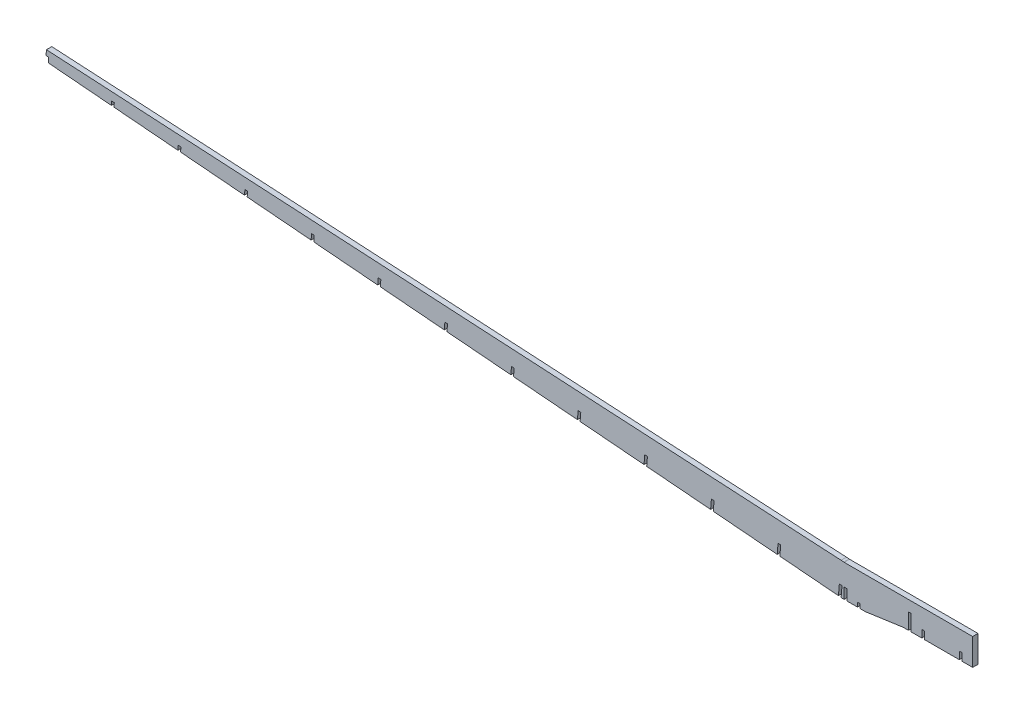
SolidWorks part; units mm, degrees
material "Balsa"
ref_plane "Front Plane" through (0, 0, 0) normal (0, 0, 1) x (1, 0, 0)
ref_plane "Top Plane" through (0, 0, 0) normal (0, 1, 0) x (1, 0, 0)
ref_plane "Right Plane" through (0, 0, 0) normal (1, 0, 0) x (0, 0, -1)
sketch "Sketch1" plane through (0, 0, 0) normal (0, 0, 1) x (1, 0, 0)
  line L0 (76.2, 56.7475) -> (76.2, 37.6975)
  line L1 (79.375, 56.7475) -> (79.375, 37.6975)
  line L2 (0, 44.0475) -> (0, 31.3475)
  line L3 (3.175, 44.0475) -> (3.175, 31.3475)
  line L4 (-5.7133, 44.4467) -> (-6.776, 31.7912)
  line L5 (-2.5494, 44.181) -> (-3.6121, 31.5255)
  line L6 (-1.4923, 31.3475) -> (25.4, 31.3475)
  line L7 (25.4, 31.3475) -> (69.85, 37.6975)
  line L8 (-2.5494, 44.181) -> (-0.424, 69.4919) construction
  line L9 (-0.424, 69.4919) -> (-3.5879, 69.7576)
  line L10 (-3.5879, 69.7576) -> (-5.7133, 44.4467) construction
  line L11 (-5.7133, 44.4467) -> (-2.5494, 44.181)
  line L12 (3.175, 44.0475) -> (3.175, 69.4475) construction
  line L13 (3.175, 69.4475) -> (0, 69.4475)
  line L14 (0, 69.4475) -> (0, 44.0475) construction
  line L15 (0, 44.0475) -> (3.175, 44.0475)
  line L16 (92.075, 37.6975) -> (92.075, 46.5875)
  line L17 (-942.8808, 122.7744) -> (-947.5199, 67.5279)
  line L18 (0, 69.4475) -> (-0.424, 69.4919)
  line L19 (3.175, 69.4475) -> (152.4, 69.4475)
  line L20 (152.4, 69.4475) -> (152.4, 37.6975)
  line L21 (152.4, 37.6975) -> (69.85, 37.6975)
  line L22 (92.075, 46.5875) -> (95.25, 46.5875)
  line L23 (95.25, 46.5875) -> (95.25, 37.6975)
  line L24 (-1.4923, 31.3475) -> (-943.9128, 110.4848)
  line L25 (79.375, 69.4475) -> (79.375, 56.7475)
  line L26 (-942.8808, 122.7744) -> (-3.5879, 69.7576)
  line L27 (136.525, 37.6975) -> (136.525, 46.5875)
  line L28 (76.2, 69.4475) -> (76.2, 56.7475)
  line L29 (79.375, 56.7475) -> (76.2, 56.7475)
  line L30 (-943.5688, 114.5813) -> (-5.7133, 44.4467)
  line L31 (136.525, 46.5875) -> (139.7, 46.5875)
  line L32 (139.7, 46.5875) -> (139.7, 37.6975)
  line L33 (15.875, 31.3475) -> (15.875, 36.4275)
  line L34 (15.875, 36.4275) -> (19.05, 36.4275)
  line L35 (19.05, 36.4275) -> (19.05, 31.3475)
  line L36 (-942.8808, 122.7744) -> (-946.0519, 122.9534)
  line L37 (-946.0519, 122.9534) -> (-946.5835, 116.6233)
  line L38 (-946.5835, 116.6233) -> (-943.4123, 116.4443)
  dimension "D3" = 76.2
  dimension "D10" = 12.3329
  dimension "D11" = 8.2219
  dimension "D2" = 25.4
  dimension "D4" = 25.4
  dimension "D5" = 12.7
  dimension "D7" = 3.175
  dimension "D9" = 3.175
  dimension "D12" = 3.175
  dimension "D6" = 19.05
  dimension "D13" = 6.35
  dimension "D14" = 12.7
  dimension "D16" = 3.175
  dimension "D17" = 3.175
  dimension "D18" = 12.7
  dimension "D19" = 12.7
  dimension "D20" = 8.89
  dimension "D21" = 8.89
  dimension "D15" = 76.2
  dimension "D22" = 12.7
  dimension "D23" = 3.175
  dimension "D24" = 5.08
  dimension "D8" = 6.35
  dimension "D25" = 3.175
  dimension "D26" = 6.35
extrude "Boss-Extrude1" add sketch "Sketch1" along normal mid plane 6.35 contours L17 L30 L11 L5 L24 L6 L2 L15 L3 L7 L21 L0 L28 L19 L13 L18 L9 L26 | L30 L17 L24 L4 | L29 L25 L19 L28 | L19 L25 L1 L21 L20 | L37 L38 L17 L36 region at (-328.9931, 77.9728, 0) region at (77.7875, 63.0975, 0) region at (115.8875, 53.8578, 0) region at (-944.7321, 119.6988, 0) region at (-395.1618, 68.9894, 0)
sketch "Sketch2" plane through (0, 0, 3.175) normal (0, 0, 1) x (1, 0, 0)
  line L2 (-73.2652, 73.2231) -> (-80.3969, -11.7061)
  line L3 (-943.5688, 114.5813) -> (-5.7133, 44.4467)
  line L6 (-76.4291, 73.4888) -> (-83.5608, -11.4404)
  line L7 (-6.776, 31.7912) -> (-943.9128, 110.4848)
  line L10 (-152.4177, 77.6821) -> (-159.3225, -4.5442)
  line L14 (-155.5816, 77.9478) -> (-162.4863, -4.2785)
  line L18 (-231.5658, 82.1932) -> (-238.251, 2.5812)
  line L22 (-234.7297, 82.4589) -> (-241.4149, 2.8469)
  line L26 (-310.7178, 86.6582) -> (-317.1769, 9.7387)
  line L30 (-313.8817, 86.9239) -> (-320.3408, 10.0043)
  line L34 (-389.8657, 91.1713) -> (-396.1056, 16.8623)
  line L38 (-393.0296, 91.437) -> (-399.2695, 17.128)
  line L42 (-469.0186, 95.6263) -> (-475.031, 24.0265)
  line L46 (-472.1824, 95.892) -> (-478.1948, 24.2921)
  line L50 (-548.1666, 100.1381) -> (-553.9596, 31.1506)
  line L54 (-551.3305, 100.4038) -> (-557.1235, 31.4163)
  line L58 (-627.3195, 104.5918) -> (-632.8849, 38.3152)
  line L62 (-630.4834, 104.8575) -> (-636.0488, 38.5809)
  line L66 (-706.4673, 109.1069) -> (-711.8138, 45.4365)
  line L70 (-709.6312, 109.3725) -> (-714.9777, 45.7022)
  line L74 (-785.6206, 113.5558) -> (-790.7389, 52.6041)
  line L78 (-788.7845, 113.8214) -> (-793.9027, 52.8697)
  line L82 (-864.7684, 118.071) -> (-869.6679, 59.7246)
  line L86 (-867.9323, 118.3366) -> (-872.8317, 59.9902)
  line L89 (-942.9091, 122.4365) -> (-947.5795, 66.8182)
  line M2 (-943.9128, 110.4848) -> (-6.776, 31.7912)
extrude "Cut-Extrude1" cut sketch "Sketch2" against normal through all contours L3 L6 L2 M2 | L3 L14 L7 L10 | L3 L22 L7 L18 | L3 L30 L7 L26 | L3 L38 L7 L34 | L3 L46 L7 L42 | L3 L54 L7 L50 | L3 L62 L7 L58 | L3 L70 L7 L66 | L3 L78 L7 L74 | L3 L86 L7 L82 region at (-77.3317, 43.7615, 3.175) region at (-156.332, 50.0322, 3.175) region at (-235.3323, 56.3029, 3.175) region at (-314.3326, 62.5736, 3.175) region at (-393.3328, 68.8442, 3.175) region at (-472.3331, 75.1149, 3.175) region at (-551.3334, 81.3856, 3.175) region at (-630.3336, 87.6563, 3.175) region at (-709.3339, 93.9269, 3.175) region at (-788.334, 100.1976, 3.175) region at (-867.3342, 106.4683, 3.175)
equation "\"D11@Sketch1\"=\"D10@Sketch1\"*(2/3)"
